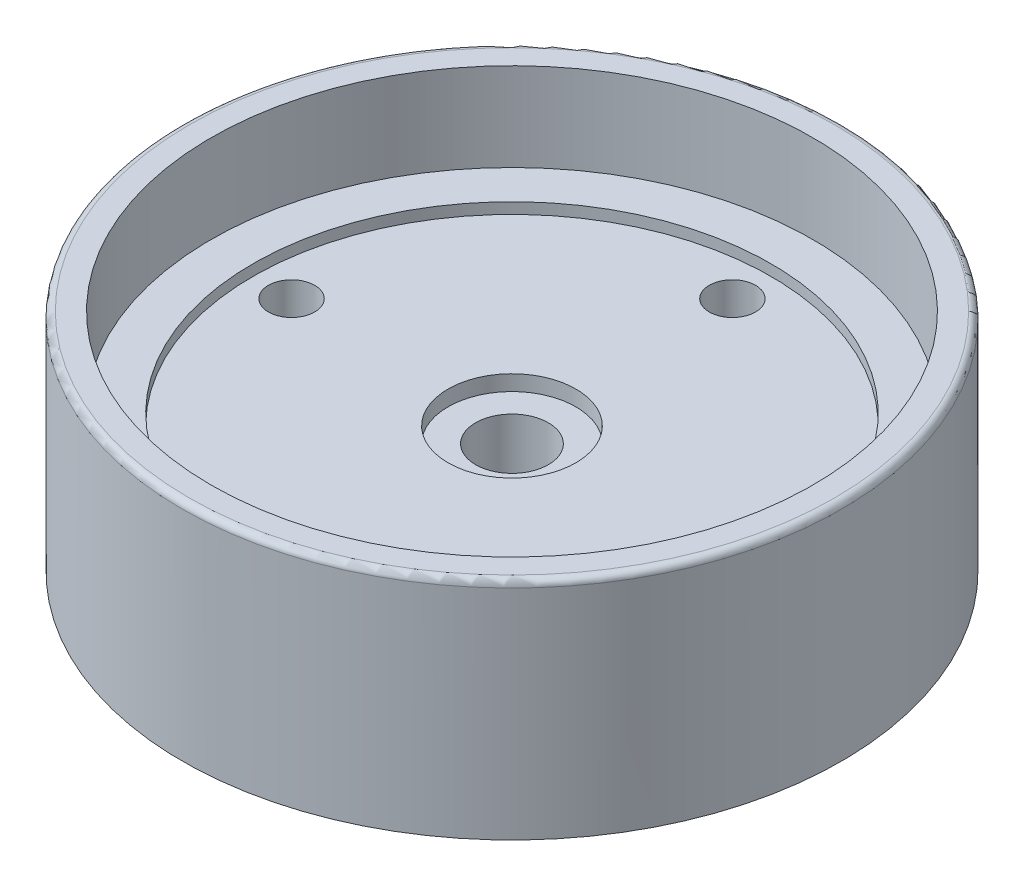
SolidWorks part; units mm, degrees
ref_plane "Front Plane" through (0, 0, 0) normal (0, 0, 1) x (1, 0, 0)
ref_plane "Top Plane" through (0, 0, 0) normal (0, 1, 0) x (1, 0, 0)
ref_plane "Right Plane" through (0, 0, 0) normal (1, 0, 0) x (0, 0, -1)
sketch "Sketch1" plane through (0, 0, 0) normal (0, 1, 0) x (1, 0, 0)
  circle A0 centre (0, 0) radius 14.95
  dimension "D1" = 29.9
extrude "Boss-Extrude1" add sketch "Sketch1" along normal blind 6.2
sketch "Sketch2" plane through (0, 6.2, 0) normal (0, 1, 0) x (1, 0, 0)
  circle A0 centre (0, 0) radius 11.75
  dimension "D1" = 23.5
extrude "Cut-Extrude1" cut sketch "Sketch2" against normal blind 0.5
sketch "Sketch3" plane through (0, 6.2, 0) normal (0, 1, 0) x (1, 0, 0)
  circle A0 centre (0, 0) radius 13.65
  circle A1 centre (0, 0) radius 14.95
  circle A2 centre (0, 0) radius 14.95 construction
  dimension "D1" = 27.3
extrude "Boss-Extrude2" add sketch "Sketch3" along normal blind 4
fillet "Fillet1" radius 0.3 1 edges at (0, 10.2, 14.95)
sketch "Sketch4" plane through (0, 5.7, 0) normal (0, 1, 0) x (1, 0, 0)
  circle A0 centre (0, 0) radius 1.65
  dimension "D1" = 3.3
extrude "Cut-Extrude2" cut sketch "Sketch4" against normal through all
ref_plane "Plane1" through (3.75, 0, 0) normal (1, 0, 0) x (0, 0, -1)
sketch "Sketch6" plane through (0, 0, 0) normal (0, -1, 0) x (1, 0, 0)
  circle A0 centre (0, 0) radius 1.65 construction
  circle A1 centre (0, 0) radius 1.65
  circle A2 centre (0, 0) radius 17.25
  dimension "D1" = 34.5
extrude "Boss-Extrude3" [suppressed] add sketch "Sketch6" along normal blind 1
ref_axis "Axis1" through (0, 9.9, 0) along (0, -1, 0)
ref_plane "Plane2" through (0, 0, 0) normal (0, 0, 1) x (0, -1, 0)
ref_plane "Plane3" through (0, 0, 12.5) normal (0, 0, 1) x (0, -1, 0)
sketch "Sketch11" plane through (0, 0, 12.5) normal (0, 0, 1) x (0, -1, 0)
  line L0 (0, 23.2225) -> (0, -23.2225) construction
  point P4 (0, 0)
ref_plane "Plane4" through (0, 2.5421, 11.9597) normal (0, 0.2079, 0.9781) x (-1, 0, 0)
sketch "Sketch9" plane through (0, 0.4189, 12.411) normal (0, 0.2079, 0.9781) x (0, -0.9781, 0.2079)
  line L0 (-11.8543, 0) -> (-2.1706, 0) construction
  line L2 (1.4283, 2.9) -> (-4.3717, 2.9) construction
  line L3 (1.4283, 2.9) -> (1.4283, -2.9) construction
  line L4 (1.4283, -2.9) -> (-4.3717, -2.9) construction
  line L5 (-4.3717, 2.9) -> (-4.3717, -2.9) construction
  line L6 (1.4283, 2.9) -> (-4.3717, -2.9) construction
  line L7 (1.4283, -2.9) -> (-4.3717, 2.9) construction
  line L8 (0.4283, 23.2225) -> (0.4283, -23.2225) construction
  circle A0 centre (-1.4717, 0) radius 1.65
  dimension "D2" = 3.3
  dimension "D1" = 5.8
  dimension "D3" = 1
ref_plane "Plane5" through (0, 2.2302, 10.4924) normal (0, 0.2079, 0.9781) x (-1, 0, 0)
ref_plane "Plane6" through (0, 0, 0) normal (-1, 0, 0) x (0, -1, 0)
ref_plane "Plane7" through (0, 0, 14.95) normal (0, 0, 1) x (1, 0, 0)
sketch "Sketch16" [suppressed] plane through (0, -1, 0) normal (0, -1, 0) x (1, 0, 0)
  line L0 (0, 0) -> (-12.1976, 12.1976) construction
  line L1 (0, 11.1539) -> (0, -11.1539) construction
  circle A0 centre (0, 0) radius 17.25 construction
  circle A1 centre (-8.5206, 8.5206) radius 1.4
  circle A2 centre (-8.5206, 8.5206) radius 2.9 construction
  circle A3 centre (0, 0) radius 14.95 construction
  dimension "D2" = 2.8
  dimension "D3" = 5.8
  dimension "D1" = 45
extrude "Cut-Extrude8" [suppressed] cut sketch "Sketch16" against normal blind 4.5
sketch "Sketch18" plane through (0, 5.7, 0) normal (0, 1, 0) x (1, 0, 0)
  circle A2 centre (0, 0) radius 2.9
  dimension "D1" = 5.8
extrude "Cut-Extrude10" cut sketch "Sketch18" against normal blind 0.7
sketch "Sketch19" plane through (0, 5.7, 0) normal (0, 1, 0) x (1, 0, 0)
  line L0 (0, 0) -> (0, 14.95) construction
  circle A0 centre (0, 0) radius 14.95 construction
  circle A1 centre (0, 10) radius 1.05
  circle A2 centre (10, 0) radius 1.05
  circle A3 centre (0, -10) radius 1.05
  circle A4 centre (-10, 0) radius 1.05
  point P8 (0, 0)
  point P9 (0, 0)
  point P17 (0, 0)
  dimension "D1" = 2.1
  dimension "D2" = 10
  dimension "D3" = 4
extrude "Cut-Extrude11" cut sketch "Sketch19" against normal through all
